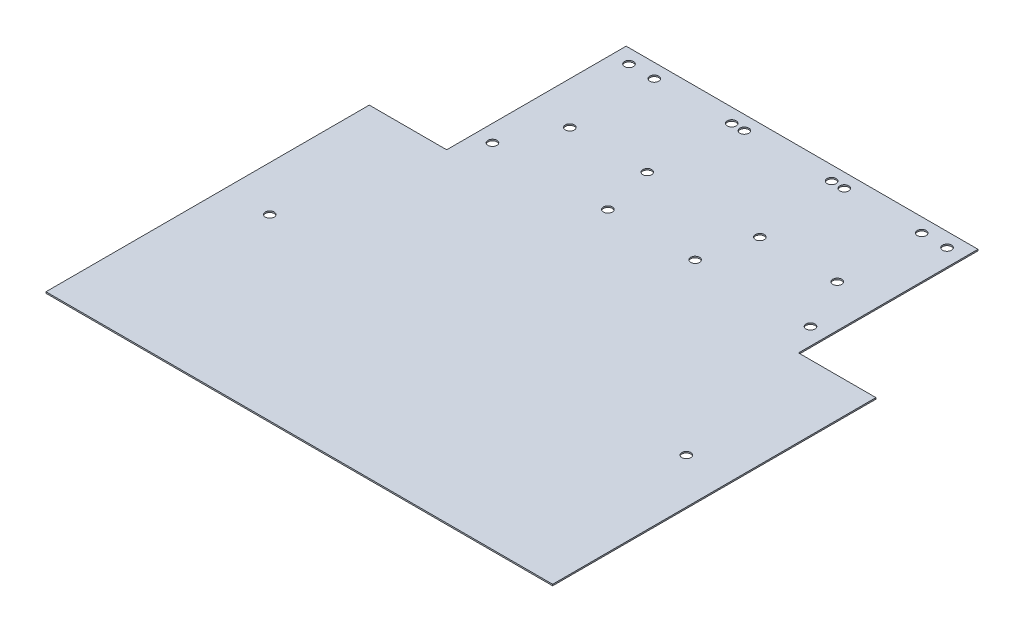
SolidWorks part; units mm, degrees
ref_plane "Alzado" through (0, 0, 0) normal (0, 0, 1) x (1, 0, 0)
ref_plane "Planta" through (0, 0, 0) normal (0, 1, 0) x (1, 0, 0)
ref_plane "Vista lateral" through (0, 0, 0) normal (1, 0, 0) x (0, 0, -1)
sketch "Croquis2" plane through (0, 0, 0) normal (0, 1, 0) x (1, 0, 0)
  line L0 (-90, 25.54) -> (-62.5, 25.54)
  line L1 (90, -89.31) -> (-90, -89.31)
  line L2 (90, -89.31) -> (90, 25.54)
  line L3 (62.5, 89.31) -> (-62.5, 89.31)
  line L4 (-90, -89.31) -> (-90, 25.54)
  line L5 (90, -89.31) -> (-62.5, 62.0208) construction
  line L6 (62.5, 62.0208) -> (-90, -89.31) construction
  line L7 (-62.5, 25.54) -> (-62.5, 89.31)
  line L8 (0, 0) -> (0, 89.31) construction
  line L9 (90, 25.54) -> (62.5, 25.54)
  line L10 (62.5, 25.54) -> (62.5, 89.31)
  point P0 (0, 0)
  dimension "D1" = 125
  dimension "D2" = 180
  dimension "D4" = 63.77
extrude "Saliente-Extruir1" add sketch "Croquis2" along normal blind 0.5
sketch "Croquis3" plane through (90, 0, 0) normal (1, 0, 0) x (0, 0, -1)
  line L0 (-89.31, 0) -> (-87.9363, 0.5)
  line L1 (-89.31, 0.5) -> (25.54, 0.5) construction
  line L2 (-87.9363, 0.5) -> (-89.31, 0.5)
  line L3 (-89.31, 0.5) -> (-89.31, 0)
  dimension "D1" = 70
extrude "Cortar-Extruir1" cut sketch "Croquis3" against normal up to next
sketch "Croquis5" plane through (0, 0.5, 0) normal (0, 1, 0) x (1, 0, 0)
  circle A0 centre (74, -25.8204) radius 1.585
sketch "Croquis6" plane through (0, 0.5, 0) normal (0, 1, 0) x (1, 0, 0)
  circle A0 centre (-56.5, 35.81) radius 1.585
  circle A1 centre (-15.5, 35.81) radius 1.585
  circle A2 centre (-15.5, 84.31) radius 1.585
  circle A3 centre (-56.5, 84.31) radius 1.585
extrude "Cortar-Extruir4" cut sketch "Croquis6" against normal up to next
sketch "Croquis7" plane through (0, 0.5, 0) normal (0, 1, 0) x (1, 0, 0)
  circle A0 centre (56.5, 35.81) radius 1.585
  circle A1 centre (15.5, 35.81) radius 1.585
  circle A2 centre (15.5, 84.31) radius 1.585
  circle A3 centre (56.5, 84.31) radius 1.585
extrude "Cortar-Extruir5" cut sketch "Croquis7" against normal up to next
mirror "Simetría3" about plane through (0, 0, 0) normal (1, 0, 0) of "Saliente-Extruir1"
sketch "Croquis8" plane through (0, 0.5, 0) normal (0, 1, 0) x (1, 0, 0)
  circle A0 centre (-20, 54.31) radius 1.585
  circle A1 centre (-47.5, 54.31) radius 1.585
  circle A2 centre (-47.5, 84.31) radius 1.585
  circle A3 centre (-20, 84.31) radius 1.585
extrude "Cortar-Extruir6" cut sketch "Croquis8" against normal up to next
mirror "Simetría4" about plane through (0, 0, 0) normal (1, 0, 0) of "Cortar-Extruir6"
sketch "Croquis9" plane through (0, 0, 0) normal (0, -1, 0) x (1, 0, 0)
  circle A0 centre (56.5, -35.81) radius 1.585
  circle A2 centre (15.5, -35.81) radius 1.585
  circle A3 centre (15.5, -84.31) radius 1.585
  circle A4 centre (56.5, -84.31) radius 1.585
extrude "Cortar-Extruir7" cut sketch "Croquis9" against normal up to next
mirror "Simetría5" about plane through (0, 0, 0) normal (1, 0, 0) of "Cortar-Extruir7"
extrude "Cortar-Extruir8" cut sketch "Croquis5" against normal up to next
mirror "Simetría6" about plane through (0, 0, 0) normal (1, 0, 0) of "Cortar-Extruir8"
